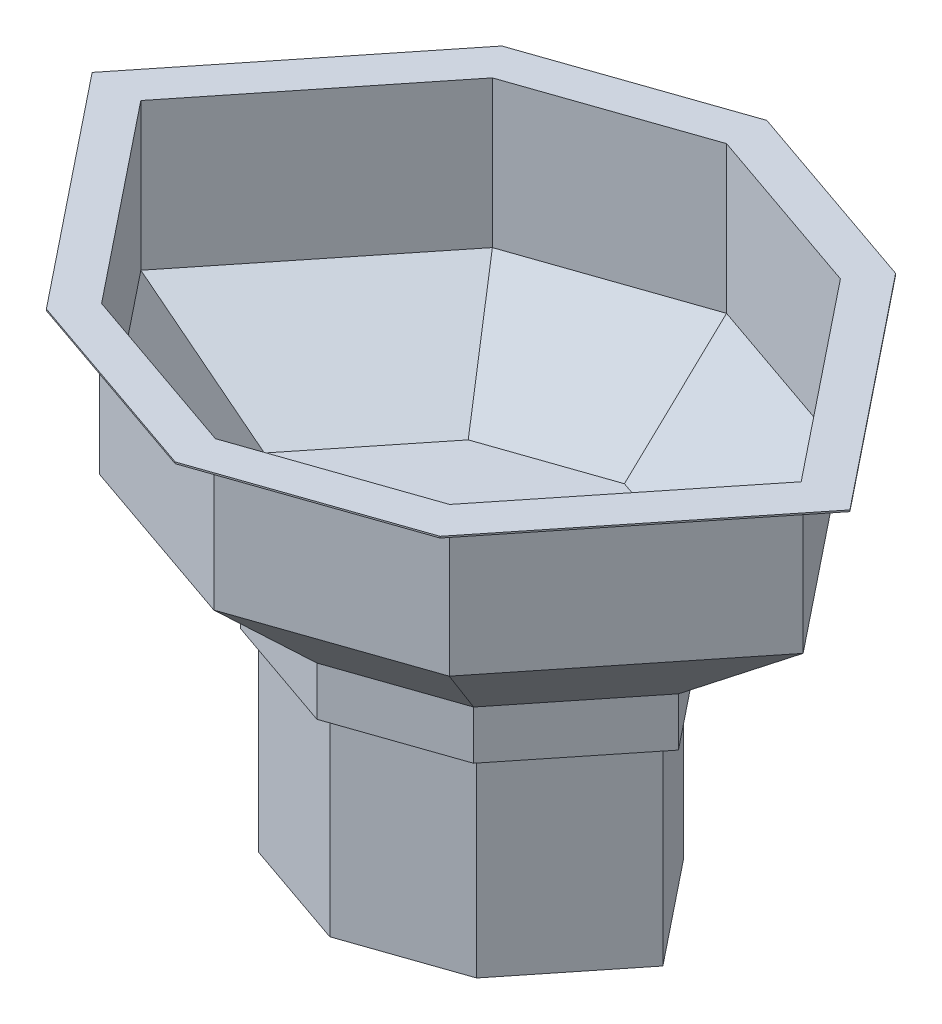
SolidWorks part; units mm, degrees
material "AISI 1020"
ref_plane "Front Plane" through (0, 0, 0) normal (0, 0, 1) x (1, 0, 0)
ref_plane "Top Plane" through (0, 0, 0) normal (0, 1, 0) x (1, 0, 0)
ref_plane "Right Plane" through (0, 0, 0) normal (1, 0, 0) x (0, 0, -1)
sketch "Sketch2" plane through (0, 0, 0) normal (0, 1, 0) x (1, 0, 0)
  line L0 (-227.7274, 215.9129) -> (-400.2698, 0)
  line L1 (-227.7274, 215.9129) -> (0, 294.6347)
  line L2 (-400.2698, 0) -> (400.2698, 0) construction
  line L3 (0, 294.6347) -> (227.7274, 215.9129)
  line L4 (-227.7274, 215.9129) -> (-227.7274, -215.9129) construction
  line L5 (-227.7274, 215.9129) -> (227.7274, 215.9129) construction
  line L6 (227.7274, -215.9129) -> (-227.7274, -215.9129) construction
  line L7 (-400.2698, 0) -> (-227.7274, -215.9129)
  line L8 (227.7274, 215.9129) -> (400.2698, 0)
  line L9 (400.2698, 0) -> (227.7274, -215.9129)
  line L10 (227.7274, 215.9129) -> (227.7274, -215.9129) construction
  line L11 (227.7274, -215.9129) -> (0, -294.6347)
  line L12 (0, -294.6347) -> (-227.7274, -215.9129)
  line L13 (0, 294.6347) -> (0, -294.6347) construction
  point P0 (0, 0)
extrude "Boss-Extrude1" add sketch "Sketch2" along normal blind 406.4
sketch "Sketch3" plane through (0, 406.4, 0) normal (0, 1, 0) x (1, 0, 0)
  line L0 (0, 321.5095) -> (-242.9779, 237.5159)
  line L1 (-242.9779, 237.5159) -> (-432.7839, 0)
  line L2 (-432.7839, 0) -> (-242.9779, -237.5159)
  line L3 (-242.9779, -237.5159) -> (0, -321.5095)
  line L4 (0, -321.5095) -> (242.9779, -237.5159)
  line L5 (242.9779, -237.5159) -> (432.7839, 0)
  line L6 (432.7839, 0) -> (242.9779, 237.5159)
  line L7 (242.9779, 237.5159) -> (0, 321.5095)
  line L8 (0, 294.6347) -> (-227.7274, 215.9129)
  line L9 (-227.7274, 215.9129) -> (-400.2698, 0)
  line L10 (-400.2698, 0) -> (-227.7274, -215.9129)
  line L11 (-227.7274, -215.9129) -> (0, -294.6347)
  line L12 (0, -294.6347) -> (227.7274, -215.9129)
  line L13 (227.7274, -215.9129) -> (400.2698, 0)
  line L14 (400.2698, 0) -> (227.7274, 215.9129)
  line L15 (227.7274, 215.9129) -> (0, 294.6347)
  line L16 (0, 294.6347) -> (-227.7274, 215.9129)
  line L17 (-227.7274, 215.9129) -> (-400.2698, 0)
  line L18 (-400.2698, 0) -> (-227.7274, -215.9129)
  line L19 (-227.7274, -215.9129) -> (0, -294.6347)
  line L20 (0, -294.6347) -> (227.7274, -215.9129)
  line L21 (227.7274, -215.9129) -> (400.2698, 0)
  line L22 (400.2698, 0) -> (227.7274, 215.9129)
  line L23 (227.7274, 215.9129) -> (0, 294.6347)
  dimension "D1" = 0
  dimension "D2" = 25.4
extrude "Boss-Extrude2" add sketch "Sketch3" along normal blind 101.6
sketch "Sketch4" plane through (0, 508, 0) normal (0, 1, 0) x (1, 0, 0)
  line L0 (-242.9779, 237.5159) -> (-432.7839, 0) construction
  line L1 (0, 321.5095) -> (-242.9779, 237.5159) construction
  line L2 (242.9779, 237.5159) -> (0, 321.5095) construction
  line L3 (432.7839, 0) -> (242.9779, 237.5159) construction
  line L4 (242.9779, -237.5159) -> (432.7839, 0) construction
  line L5 (0, -321.5095) -> (242.9779, -237.5159) construction
  line L6 (-242.9779, -237.5159) -> (0, -321.5095) construction
  line L7 (-432.7839, 0) -> (-242.9779, -237.5159) construction
  line L8 (-242.9779, 237.5159) -> (-432.7839, 0)
  line L9 (0, 321.5095) -> (-242.9779, 237.5159)
  line L10 (242.9779, 237.5159) -> (0, 321.5095)
  line L11 (432.7839, 0) -> (242.9779, 237.5159)
  line L12 (242.9779, -237.5159) -> (432.7839, 0)
  line L13 (0, -321.5095) -> (242.9779, -237.5159)
  line L14 (-242.9779, -237.5159) -> (0, -321.5095)
  line L15 (-432.7839, 0) -> (-242.9779, -237.5159)
ref_plane "Plane1" through (0, 711.2, 0) normal (0, 1, 0) x (1, 0, 0)
sketch "Sketch5" plane through (0, 711.2, 0) normal (0, 1, 0) x (1, 0, 0)
  line L0 (0, 321.5095) -> (-242.9779, 237.5159) construction
  line L1 (242.9779, 237.5159) -> (0, 321.5095) construction
  line L2 (432.7839, 0) -> (242.9779, 237.5159) construction
  line L3 (242.9779, -237.5159) -> (432.7839, 0) construction
  line L4 (0, -321.5095) -> (242.9779, -237.5159) construction
  line L5 (-242.9779, -237.5159) -> (0, -321.5095) construction
  line L6 (-432.7839, 0) -> (-242.9779, -237.5159) construction
  line L7 (-242.9779, 237.5159) -> (-432.7839, 0) construction
  line L8 (0, 321.5095) -> (-242.9779, 237.5159) construction
  line L9 (242.9779, 237.5159) -> (0, 321.5095) construction
  line L10 (432.7839, 0) -> (242.9779, 237.5159) construction
  line L11 (242.9779, -237.5159) -> (432.7839, 0) construction
  line L12 (0, -321.5095) -> (242.9779, -237.5159) construction
  line L13 (-242.9779, -237.5159) -> (0, -321.5095) construction
  line L14 (-432.7839, 0) -> (-242.9779, -237.5159) construction
  line L15 (-242.9779, 237.5159) -> (-432.7839, 0) construction
  line L16 (0, 536.5079) -> (-364.982, 410.3394)
  line L17 (-364.982, 410.3394) -> (-692.8964, 0)
  line L18 (-692.8964, 0) -> (-364.982, -410.3394)
  line L19 (-364.982, -410.3394) -> (0, -536.5079)
  line L20 (0, -536.5079) -> (364.982, -410.3394)
  line L21 (364.982, -410.3394) -> (692.8964, 0)
  line L22 (692.8964, 0) -> (364.982, 410.3394)
  line L23 (364.982, 410.3394) -> (0, 536.5079)
  dimension "D1" = 203.2
loft "Loft1" add profiles "Sketch5", "Sketch4" connector at (-692.8964, 711.2, 0) connector at (-432.7839, 508, 0)
sketch "Sketch6" plane through (0, 711.2, 0) normal (0, 1, 0) x (1, 0, 0)
  line L6 (-364.982, -410.3394) -> (0, -536.5079)
  line L7 (-364.982, -410.3394) -> (0, -536.5079)
  line L8 (0, -536.5079) -> (364.982, -410.3394)
  line L9 (0, -536.5079) -> (364.982, -410.3394)
  line L10 (364.982, -410.3394) -> (692.8964, 0)
  line L11 (364.982, -410.3394) -> (692.8964, 0)
  line L12 (692.8964, 0) -> (364.982, 410.3394)
  line L13 (692.8964, 0) -> (364.982, 410.3394)
  line L14 (364.982, 410.3394) -> (0, 536.5079)
  line L15 (364.982, 410.3394) -> (0, 536.5079)
  line L16 (0, 536.5079) -> (-364.982, 410.3394)
  line L17 (0, 536.5079) -> (-364.982, 410.3394)
  line L26 (-364.982, 410.3394) -> (-692.8964, 0)
  line L27 (-364.982, 410.3394) -> (-692.8964, 0)
  line L28 (-692.8964, 0) -> (-364.982, -410.3394)
  line L29 (-692.8964, 0) -> (-364.982, -410.3394)
  dimension "D1" = 0
extrude "Boss-Extrude3" add sketch "Sketch6" along normal blind 304.8
sketch "Sketch7" plane through (0, 1016, 0) normal (0, 1, 0) x (1, 0, 0)
  line L0 (-790.4386, 0) -> (-410.7336, -475.1482)
  line L1 (-410.7336, -475.1482) -> (0, -617.1323)
  line L2 (0, -617.1323) -> (410.7336, -475.1482)
  line L3 (410.7336, -475.1482) -> (790.4386, 0)
  line L4 (790.4386, 0) -> (410.7336, 475.1482)
  line L5 (410.7336, 475.1482) -> (0, 617.1323)
  line L6 (0, 617.1323) -> (-410.7336, 475.1482)
  line L7 (-410.7336, 475.1482) -> (-790.4386, 0)
  line L8 (-692.8964, 0) -> (-364.982, -410.3394)
  line L9 (-364.982, -410.3394) -> (0, -536.5079)
  line L10 (0, -536.5079) -> (364.982, -410.3394)
  line L11 (364.982, -410.3394) -> (692.8964, 0)
  line L12 (692.8964, 0) -> (364.982, 410.3394)
  line L13 (364.982, 410.3394) -> (0, 536.5079)
  line L14 (0, 536.5079) -> (-364.982, 410.3394)
  line L15 (-364.982, 410.3394) -> (-692.8964, 0)
  line L16 (-692.8964, 0) -> (-364.982, -410.3394) construction
  line L17 (-364.982, -410.3394) -> (0, -536.5079) construction
  line L18 (0, -536.5079) -> (364.982, -410.3394) construction
  line L19 (364.982, -410.3394) -> (692.8964, 0) construction
  line L20 (692.8964, 0) -> (364.982, 410.3394) construction
  line L21 (364.982, 410.3394) -> (0, 536.5079) construction
  line L22 (0, 536.5079) -> (-364.982, 410.3394) construction
  line L23 (-364.982, 410.3394) -> (-692.8964, 0) construction
  dimension "D1" = 0
  dimension "D2" = 76.2
extrude "Boss-Extrude4" add sketch "Sketch7" along normal blind 3.175
shell "Shell3" thickness 3.175 removed face at (0, 1019.175, 0)
